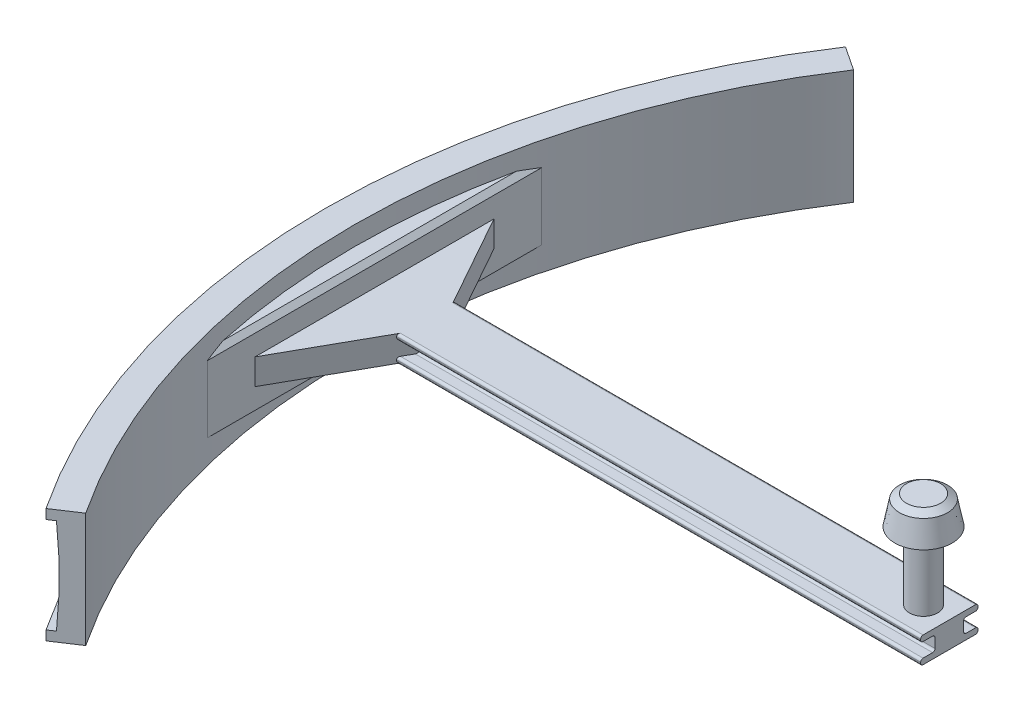
SolidWorks part; units mm, degrees
ref_plane "Front Plane" through (0, 0, 0) normal (0, 0, 1) x (1, 0, 0)
ref_plane "Top Plane" through (0, 0, 0) normal (0, 1, 0) x (1, 0, 0)
ref_plane "Right Plane" through (0, 0, 0) normal (1, 0, 0) x (0, 0, -1)
sketch "Sketch1" plane through (0, 0, 0) normal (0, 0, 1) x (1, 0, 0)
  line L0 (0, 12.464) -> (0, 0) construction
  line L1 (0, 0) -> (-94.3165, 0) construction
  line L2 (15, 24.4424) -> (15, -18.6151) construction
  line L3 (-60, 5) -> (-60.7913, 5)
  line L4 (-60.7913, 5) -> (-60.7913, 6)
  line L5 (-60.7913, 6) -> (-57.7913, 6)
  line L6 (-57.7913, 6) -> (-57.7913, -6)
  line L7 (-60.7913, -6) -> (-57.7913, -6)
  line L8 (-60.7913, -5) -> (-60.7913, -6)
  line L9 (-60, -5) -> (-60.7913, -5)
  arc A0 (-60, -5) -> (-60, 5) centre (-119.7913, 0) ccw
  point P14 (-57.7913, 0)
  dimension "D6" = 60
  dimension "D1" = 15
  dimension "D2" = 5
  dimension "D3" = 60
  dimension "D4" = 3
  dimension "D7" = 1
revolve "Revolve1" add sketch "Sketch1" angle 67 mid plane about L2
sketch "Sketch2" plane through (0, 0, 0) normal (1, 0, 0) x (0, 0, -1)
  line L0 (0, 6) -> (0, -6) construction
  line L1 (40.1762, 6) -> (-40.1762, 6) construction
  line L2 (-40.1762, -6) -> (40.1762, -6) construction
  line L3 (2.75, 1.35) -> (-2.75, 1.35)
  line L4 (-3, 1.1) -> (-3, 1)
  line L5 (-2.75, 0.75) -> (-1.75, 0.75)
  line L6 (-1.5, 0.5) -> (-1.5, -0.5)
  line L7 (-1.75, -0.75) -> (-2.75, -0.75)
  line L8 (-3, -1) -> (-3, -1.1)
  line L9 (-2.75, -1.35) -> (2.75, -1.35)
  line L10 (0, 0) -> (5.9529, 0) construction
  line L11 (3, -1) -> (3, -1.1)
  line L12 (1.75, -0.75) -> (2.75, -0.75)
  line L13 (1.5, 0.5) -> (1.5, -0.5)
  line L14 (2.75, 0.75) -> (1.75, 0.75)
  line L15 (3, 1.1) -> (3, 1)
  arc A0 (-1.5, -0.5) -> (-1.75, -0.75) centre (-1.75, -0.5) cw
  arc A1 (-1.75, 0.75) -> (-1.5, 0.5) centre (-1.75, 0.5) cw
  arc A2 (-3, -1.1) -> (-2.75, -1.35) centre (-2.75, -1.1) ccw
  arc A3 (-2.75, -0.75) -> (-3, -1) centre (-2.75, -1) ccw
  arc A4 (-3, 1) -> (-2.75, 0.75) centre (-2.75, 1) ccw
  arc A5 (-2.75, 1.35) -> (-3, 1.1) centre (-2.75, 1.1) ccw
  arc A6 (2.75, 1.35) -> (3, 1.1) centre (2.75, 1.1) cw
  arc A7 (3, 1) -> (2.75, 0.75) centre (2.75, 1) cw
  arc A8 (2.75, -0.75) -> (3, -1) centre (2.75, -1) cw
  arc A9 (3, -1.1) -> (2.75, -1.35) centre (2.75, -1.1) cw
  arc A10 (1.75, 0.75) -> (1.5, 0.5) centre (1.75, 0.5) ccw
  arc A11 (1.5, -0.5) -> (1.75, -0.75) centre (1.75, -0.5) ccw
  point P6 (3, 1.35)
  point P14 (0, 1.35)
  point P20 (-1.5, -0.75)
  point P23 (-1.5, 0.75)
  point P31 (-3, 0.75)
  point P34 (-3, 1.35)
  point P53 (0, -1.35)
  point P54 (3, 0.75)
  point P55 (1.5, 0.75)
  point P56 (1.5, -0.75)
  dimension "D5" = 0.25
  dimension "D6" = 0.25
  dimension "D1" = 3
  dimension "D2" = 0.6
  dimension "D3" = 1.5
  dimension "D4" = 1.5
extrude "Boss-Extrude1" add sketch "Sketch2" against normal up to surface and the other way blind 4.5 up to face at (-51.7455, 0, 0)
sketch "Sketch3" plane through (0, 0, 0) normal (0, 1, 0) x (1, 0, 0)
  line L0 (-55.6564, 17.5) -> (-55.6564, -17.5)
  line L1 (-55.6564, 0) -> (0, 0) construction
  arc A0 (-45.6996, 40.1762) -> (-45.6996, -40.1762) centre (15, 0) ccw construction
  arc A1 (-55.6564, 17.5) -> (-55.6564, -17.5) centre (15, 0) ccw
  dimension "D1" = 35
extrude "Boss-Extrude2" add sketch "Sketch3" along normal mid plane 8
sketch "Sketch4" plane through (0, 0, 0) normal (0, 1, 0) x (1, 0, 0)
  line L0 (-55.6564, -17.5) -> (-55.6564, 17.5) construction
  line L1 (-55.6564, -12.5) -> (-55.6564, 12.5)
  line L2 (-55.6564, 12.5) -> (-48.6564, 0)
  line L3 (-48.6564, 0) -> (-55.6564, -12.5)
  line L4 (-55.6564, 0) -> (-48.6564, 0) construction
  dimension "D1" = 12.5
  dimension "D2" = 12.5
  dimension "D3" = 7
extrude "Boss-Extrude3" add sketch "Sketch4" along normal mid plane 2.7
chamfer "Chamfer1" distance 0.5 angle 45 2 edges at (-55.6564, -4, 0) (-55.6564, 4, 0)
sketch "Sketch5" plane through (0, 1.35, 0) normal (0, 1, 0) x (1, 0, 0)
  line L0 (0, 0) -> (1.8, 0) construction
  circle A0 centre (1.8, 0) radius 1.475
  dimension "D1" = 2.95
  dimension "D2" = 1.8
extrude "Boss-Extrude4" add sketch "Sketch5" along normal blind 7.1
sketch "Sketch6" plane through (0, 8.45, 0) normal (0, 1, 0) x (1, 0, 0)
  circle A0 centre (1.8, 0) radius 3
  dimension "D1" = 6
extrude "Boss-Extrude5" add sketch "Sketch6" along normal blind 3 draft 11
chamfer "Chamfer2" distance 0.5 angle 45 1 edges at (1.8, 11.45, 2.4169) first distance on face at (1.8, 11.45, 2.4169)
